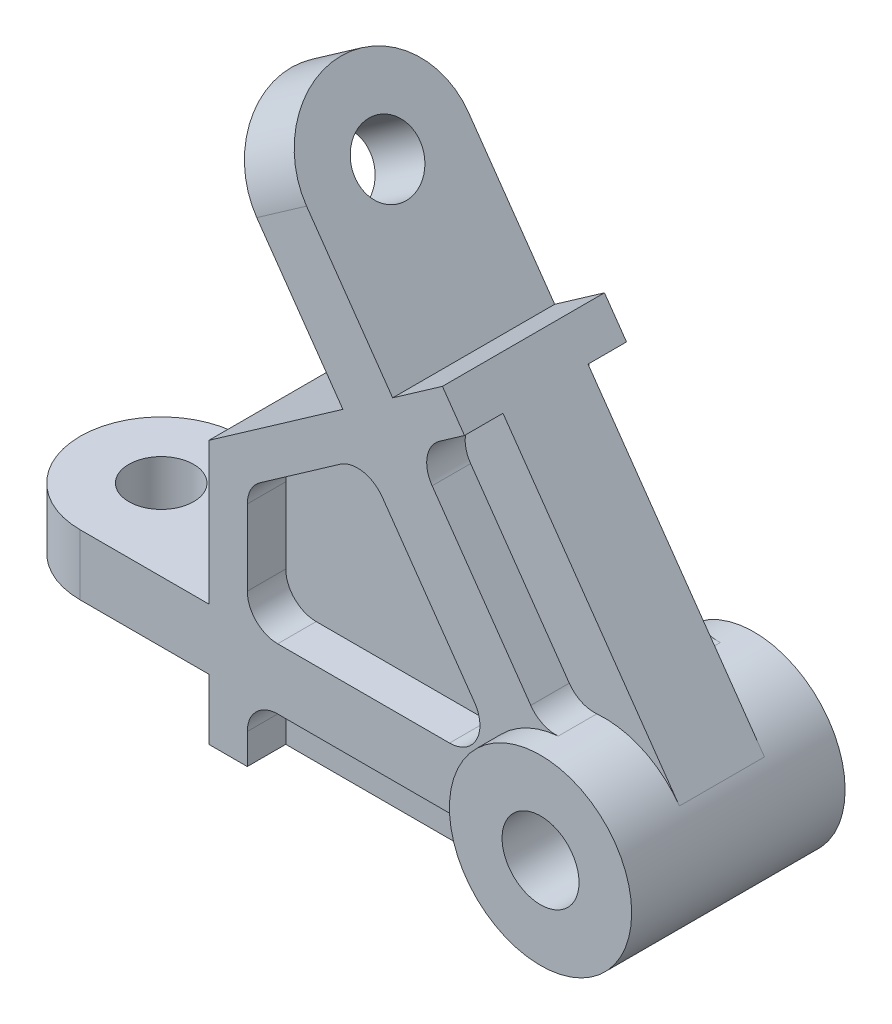
SolidWorks part; units mm, degrees
note: The reader was unsure of these and kept them because the rebuilt part matched: shared geometry of "Esquisse2<5>".
material "Alliage 1060"
ref_plane "Plan de face" through (0, 0, 0) normal (0, 0, 1) x (1, 0, 0)
ref_plane "Plan de dessus" through (0, 0, 0) normal (0, 1, 0) x (1, 0, 0)
ref_plane "Plan de droite" through (0, 0, 0) normal (1, 0, 0) x (0, 0, -1)
sketch "Esquisse2" plane through (0, 0, 0) normal (0, 0, 1) x (1, 0, 0)
  line L0 (0, 0) -> (-122.6748, 175.1977) construction
  line L1 (0, 0) -> (-230.8612, 0) construction
  line L2 (0, -22.5) -> (-88.25, -22.5)
  line L3 (-88.25, -22.5) -> (-88.25, -7.5)
  line L4 (-88.25, -7.5) -> (-120, -7.5)
  line L5 (-120, -7.5) -> (-120, 7.5)
  line L6 (-120, 7.5) -> (-88.25, 7.5)
  line L7 (-88.25, 7.5) -> (-88.25, 42.5)
  line L8 (-88.25, 42.5) -> (-55.1455, 65.68)
  line L9 (-55.1455, 65.68) -> (-76.4068, 96.0443)
  line L10 (-76.4068, 96.0443) -> (-64.1195, 104.6479)
  line L11 (-64.1195, 104.6479) -> (-42.8582, 74.2837)
  line L12 (-42.8582, 74.2837) -> (-30.5709, 82.8873)
  line L13 (-30.5709, 82.8873) -> (18.4309, 12.9055)
  circle A0 centre (0, 0) radius 22.5
  circle A1 centre (0, 0) radius 9.5
  dimension "D2" = 45
  dimension "D3" = 19
  dimension "D4" = 35
  dimension "D5" = 15
  dimension "D6" = 122.5
  dimension "D7" = 120
  dimension "D8" = 31.75
  dimension "D1" = 55
extrude "Boss.-Extru.1" add sketch "Esquisse2" along normal mid plane 40 contours A0 L13 L12 L11 L10 L9 L8 L7 L6 L5 L4 L3 L2
extrude "Boss.-Extru.2" add sketch "Esquisse2<5>" along normal offset from surface 6.35 and the other way offset from surface (26.35 mm away) 6.35 contours A0 A1 up to face at (-67.1418, 34.5489, 20) offset beyond the face yes other way up to face at (-67.1418, 34.5489, -20)
sketch "Esquisse2<5>" plane through (0, 0, 0) normal (0, 0, 1) x (1, 0, 0) same geometry as "Esquisse2"
sketch "Esquisse3" plane through (0, -7.5, 0) normal (0, -1, 0) x (1, 0, 0)
  line L0 (-120, 20) -> (-120, -20) construction
  line L1 (-120, 20) -> (-120, -20)
  arc A0 (-120, 20) -> (-120, -20) centre (-120, 0) ccw
extrude "Boss.-Extru.3" add sketch "Esquisse3" against normal up to surface (15 mm away) up to face at (-104.125, 7.5, 0)
sketch "Esquisse4" plane through (6.1436, 4.3018, 0) normal (0.8192, 0.5736, 0) x (0, 0, -1)
  line L0 (-20, 122.5) -> (20, 122.5) construction
  line L1 (-20, 122.5) -> (20, 122.5)
  arc A0 (-20, 122.5) -> (20, 122.5) centre (0, 122.5) cw
extrude "Boss.-Extru.4" add sketch "Esquisse4" against normal up to surface (15 mm away) up to face at (-65.7761, 80.8622, 0)
sketch "Esquisse5" plane through (6.1436, 4.3018, 0) normal (0.8192, 0.5736, 0) x (0, 0, -1)
  circle A0 centre (0, 122.5) radius 8
  dimension "D1" = 16
extrude "Enlèv. mat.-Extru.1" cut sketch "Esquisse5" against normal through all
sketch "Esquisse6" plane through (0, -7.5, 0) normal (0, -1, 0) x (1, 0, 0)
  circle A0 centre (-120, 0) radius 8
  dimension "D1" = 16
extrude "Enlèv. mat.-Extru.2" cut sketch "Esquisse6" against normal through all
sketch "Esquisse7" plane through (0, 0, 20) normal (0, 0, 1) x (1, 0, 0)
  line L0 (0, 0) -> (-120, 0) construction
  line L1 (0, 0) -> (-70.2631, 100.3461) construction
  line L2 (-76.4068, 96.0443) -> (-64.1195, 104.6479) construction
  line L3 (-120, -7.5) -> (-120, 7.5) construction
  line L9 (-37.4092, 66.5017) -> (-25.1219, 75.1054)
  line L10 (-31.2656, 70.8036) -> (-25.1219, 75.1054)
  line L12 (-82.801, 34.7181) -> (-49.6965, 57.8981)
  line L13 (-75.5518, 39.794) -> (-55.8401, 53.5963)
  line L15 (-78.75, 7.5) -> (-78.75, 42.5)
  line L16 (-78.75, 15) -> (-78.75, 33.6504)
  line L17 (-71.25, -7.5) -> (-25.9808, -7.5)
  line L18 (-78.75, -22.5) -> (-78.75, -7.5)
  line L19 (-78.75, -22.5) -> (-78.75, -15)
  line L20 (-71.25, 7.5) -> (-28.8147, 7.5)
  line L21 (-33.1074, 60.3581) -> (-8.7583, 25.584)
  line L22 (-45.3947, 51.7545) -> (-22.6711, 19.3018)
  line L23 (-78.75, -22.5) -> (0, -22.5)
  line L24 (-25.1219, 75.1054) -> (18.4309, 12.9055)
  arc A0 (18.4309, 12.9055) -> (0, -22.5) centre (0, 0) ccw construction
  arc A1 (18.4309, 12.9055) -> (-1.961, 22.4144) centre (0, 0) ccw
  arc A2 (-19.4856, -11.25) -> (0, -22.5) centre (0, 0) ccw
  arc A4 (-8.7583, 25.584) -> (-1.961, 22.4144) centre (-2.6147, 29.8858) ccw
  arc A5 (-31.2656, 70.8036) -> (-33.1074, 60.3581) centre (-26.9637, 64.6599) ccw
  arc A6 (-78.75, -15) -> (-71.25, -7.5) centre (-71.25, -15) cw
  arc A7 (-25.9808, -7.5) -> (-19.4856, -11.25) centre (-25.9808, -15) cw
  arc A8 (-55.8401, 53.5963) -> (-45.3947, 51.7545) centre (-51.5383, 47.4526) cw
  arc A9 (-75.5518, 39.794) -> (-78.75, 33.6504) centre (-71.25, 33.6504) ccw
  arc A10 (-78.75, 15) -> (-71.25, 7.5) centre (-71.25, 15) ccw
  arc A11 (-28.8147, 7.5) -> (-22.6711, 19.3018) centre (-28.8147, 15) ccw
  point P34 (-21.2132, -7.5)
  dimension "D5" = 7.5
  dimension "D6" = 7.5
  dimension "D7" = 7.5
  dimension "D1" = 9.5
  dimension "D2" = 9.5
  dimension "D3" = 9.5
  dimension "D4" = 9.5
extrude "Enlèv. mat.-Extru.3" cut sketch "Esquisse7" against normal blind 9.5
mirror "Symétrie1" about plane through (0, 0, 0) normal (0, 0, 1) of "Enlèv. mat.-Extru.3"
equation "\"A\" = 122.5"
equation "\"B\" = 15"
equation "\"C\" = 55"
equation "\"D5@Esquisse2\"=\"B\""
equation "\"D6@Esquisse2\"=\"A\""
equation "\"D1@Boss.-Extru.1\"=\"A\""
equation "\"D1@Esquisse2\"=\"C\""
